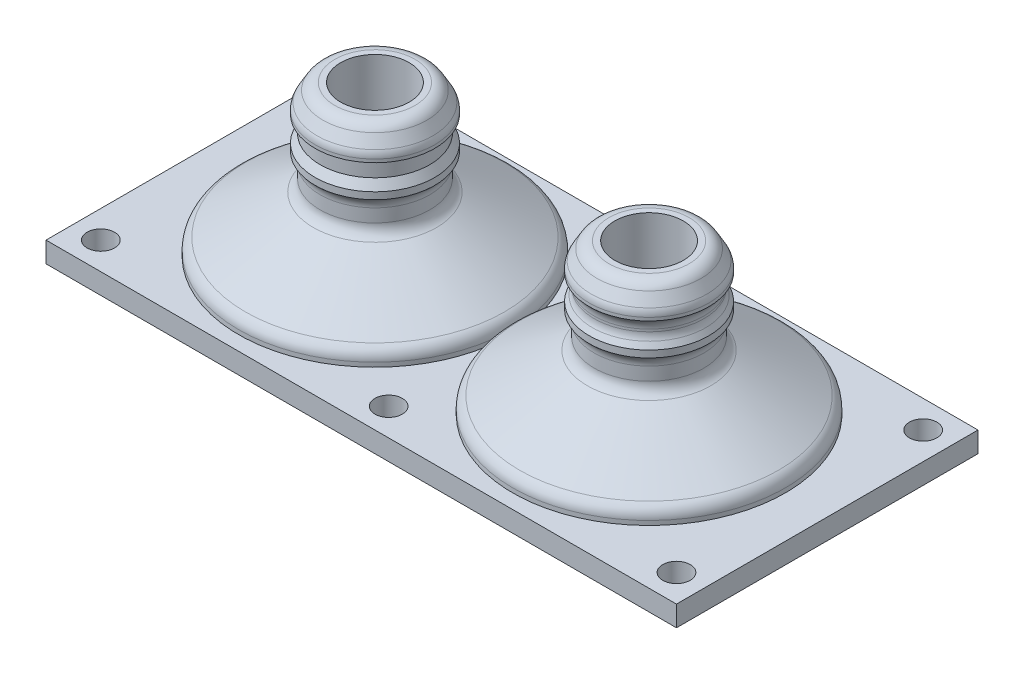
SolidWorks part; units mm, degrees
ref_plane "Front Plane" through (0, 0, 0) normal (0, 0, 1) x (1, 0, 0)
ref_plane "Top Plane" through (0, 0, 0) normal (0, 1, 0) x (1, 0, 0)
ref_plane "Right Plane" through (0, 0, 0) normal (1, 0, 0) x (0, 0, -1)
sketch "Sketch1" plane through (0, 0, 0) normal (0, 1, 0) x (1, 0, 0)
  line L0 (0, 0) -> (46, 0) construction
  line L1 (-46, -22) -> (46, -22)
  line L2 (-46, -22) -> (-46, 22)
  line L3 (-46, 22) -> (46, 22)
  line L4 (46, -22) -> (46, 22)
  line L5 (-46, -22) -> (46, 22) construction
  line L6 (-46, 22) -> (46, -22) construction
  line L7 (0, 0) -> (0, 22) construction
  line L8 (0, 18) -> (46, 18) construction
  circle A0 centre (-20, 0) radius 17
  circle A1 centre (20, 0) radius 17
  circle A2 centre (0, 18) radius 2
  circle A4 centre (-42, 18) radius 2
  circle A5 centre (-42, -18) radius 2
  circle A6 centre (42, 18) radius 2
  circle A7 centre (0, -18) radius 2
  circle A8 centre (42, -18) radius 2
  point P0 (0, 0)
  point P25 (40.4906, 0)
  point P27 (0, 0)
  dimension "D2" = 34
  dimension "D6" = 4
  dimension "D1" = 40
  dimension "D3" = 22
  dimension "D4" = 26
  dimension "D5" = 18
  dimension "D7" = 42
extrude "Boss-Extrude1" add sketch "Sketch1" along normal blind 3
sketch "Sketch2" plane through (0, 3, 0) normal (0, 1, 0) x (1, 0, 0)
  point P0 (-20, 0)
  point P1 (20, 0)
sketch3d "3DSketch3"
  line L0 (-20, 3, 0) -> (-20, 35.1077, 0) construction
  line L2 (-3, 3, 0) -> (-15, 9.9282, 0)
  line L3 (-15, 9.9282, 0) -> (-15, 24.9282, 0)
  line L4 (-15, 24.9282, 0) -> (-13, 24.9282, 0)
  line L6 (-13, 24.9282, 0) -> (-11.275, 21.9404, 0)
  line L7 (-11.275, 21.9404, 0) -> (-11.275, 20.9404, 0)
  line L8 (-11.275, 20.9404, 0) -> (-12, 20.5218, 0)
  line L9 (-12, 20.5218, 0) -> (-12, 18.5218, 0)
  line L11 (-12, 11.6603, 0) -> (-0.1, 4.7898, 0)
  line L12 (-0.1, 4.7898, 0) -> (-0.1, 3, 0)
  line L13 (-0.1, 3, 0) -> (-3, 3, 0)
  line L14 (-12, 18.5218, 0) -> (-11.275, 17.2661, 0)
  line L15 (-11.275, 17.2661, 0) -> (-11.275, 16.2661, 0)
  line L16 (-11.275, 16.2661, 0) -> (-12, 15.8475, 0)
  line L17 (-12, 15.8475, 0) -> (-12, 11.6603, 0)
  circle A1 centre (-20, 3, 0) radius 17 construction
  point P29 (-20, 20, 0)
  dimension "D1" = 17.45
  dimension "D2" = 16
  dimension "D3" = 10
  dimension "D4" = 3
  dimension "D5" = 2.9
  dimension "D6" = 120
  dimension "D7" = 1
  dimension "D8" = 150
  dimension "D9" = 2
  dimension "D10" = 2
  dimension "D11" = 150
  dimension "D12" = 15
revolve "Revolve1" add sketch "3DSketch3" angle 360 about L0
sketch3d "3DSketch5"
  line L5 (12.0139, 26.4593, 0) -> (24.0327, 41.8243, 0) construction
  line L21 (20, 3, 0) -> (20, 35.1077, 0) construction
  line L22 (37, 3, 0) -> (25, 9.9282, 0)
  line L23 (25, 9.9282, 0) -> (25, 24.9282, 0)
  line L24 (25, 24.9282, 0) -> (27, 24.9282, 0)
  line L25 (27, 24.9282, 0) -> (28.725, 21.9404, 0)
  line L26 (28.725, 21.9404, 0) -> (28.725, 20.9404, 0)
  line L27 (28.725, 20.9404, 0) -> (28, 20.5218, 0)
  line L28 (28, 20.5218, 0) -> (28, 18.5218, 0)
  line L29 (28, 11.6603, 0) -> (39.9, 4.7898, 0)
  line L30 (39.9, 4.7898, 0) -> (39.9, 3, 0)
  line L31 (39.9, 3, 0) -> (37, 3, 0)
  line L32 (28, 18.5218, 0) -> (28.725, 17.2661, 0)
  line L33 (28.725, 17.2661, 0) -> (28.725, 16.2661, 0)
  line L34 (28.725, 16.2661, 0) -> (28, 15.8475, 0)
  line L35 (28, 15.8475, 0) -> (28, 11.6603, 0)
  point P1 (18.0233, 34.1418, 0)
revolve "Revolve8" add sketch "3DSketch5" angle 360 about L21
fillet "Fillet12" radius 2 16 edges at (20, 3, -17) (20, 9.9282, -5) (-20, 3, -17) (-20, 9.9282, -5) (20, 24.9282, -7) (20, 21.9404, -8.725) (-20, 24.9282, -7) (-20, 21.9404, -8.725) (-20, 15.8475, -8) (20, 15.8475, -8) (20, 20.5218, -8) (20, 18.5218, -8) (20, 11.6603, -8) (20, 4.7898, -19.9) (-20, 11.6603, -8) (-20, 4.7898, -19.9)
